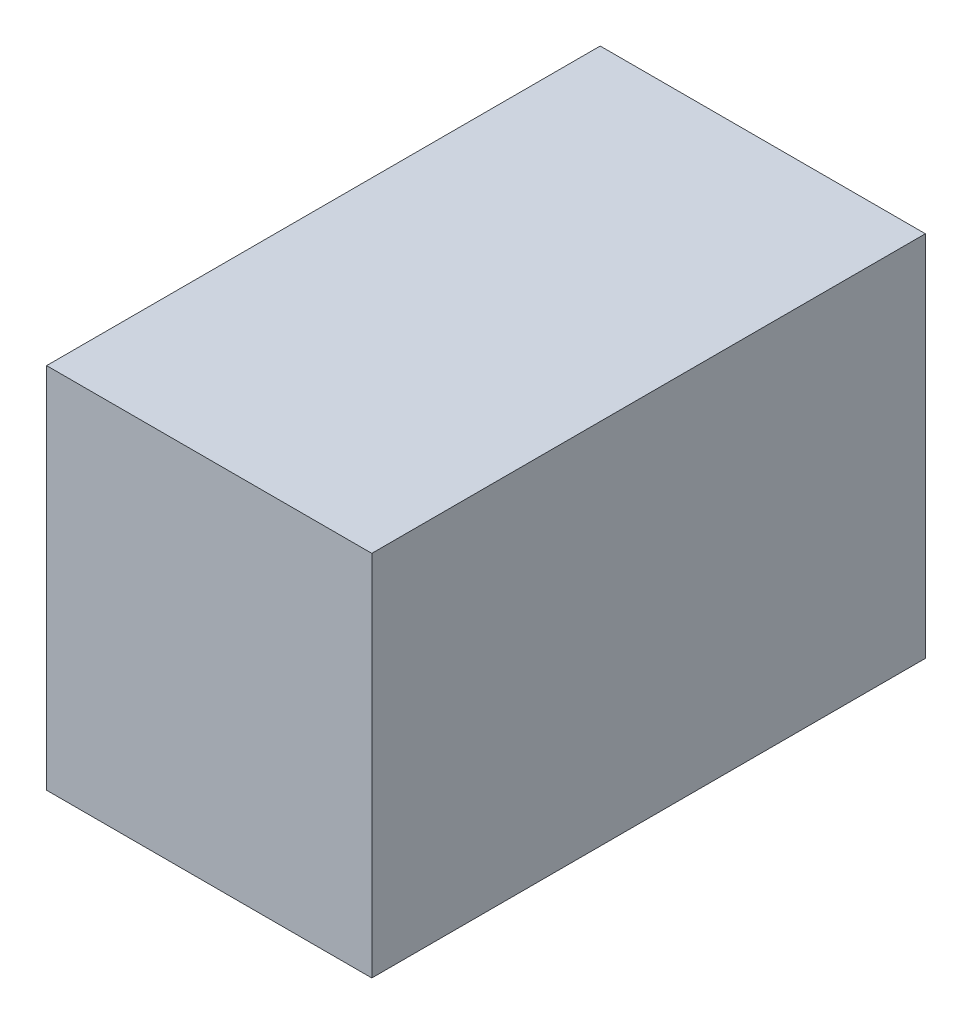
SolidWorks part; units mm, degrees
ref_plane "Front Plane" through (0, 0, 0) normal (0, 0, 1) x (1, 0, 0)
ref_plane "Top Plane" through (0, 0, 0) normal (0, 1, 0) x (1, 0, 0)
ref_plane "Right Plane" through (0, 0, 0) normal (1, 0, 0) x (0, 0, -1)
sketch "Sketch4" plane through (0, 0, 0) normal (1, 0, 0) x (0, 0, -1)
  line L1 (-15.875, 9.875) -> (15.875, 9.875)
  line L2 (-15.875, 9.875) -> (-15.875, -9.875)
  line L3 (-15.875, -9.875) -> (15.875, -9.875)
  line L4 (15.875, 9.875) -> (15.875, -9.875)
  line L5 (-15.875, 9.875) -> (15.875, -9.875) construction
  line L6 (-15.875, -9.875) -> (15.875, 9.875) construction
  point P0 (0, 0)
  dimension "D1" = 31.75
  dimension "D2" = 19.75
extrude "Boss-Extrude1" add sketch "Sketch4" along normal blind 19
shell "Shell1" thickness 2 removed face at (0, 0, 0) outward yes
sketch "Sketch5" plane through (0, 0, -17.875) normal (0, 0, -1) x (-1, 0, 0)
  line L0 (0, -11.875) -> (0, 11.875) construction
  line L1 (0, 9.875) -> (-12, 9.875)
  line L2 (-12, 9.875) -> (-12, -9.875)
  line L3 (-12, -9.875) -> (0, -9.875)
  line L4 (-21, 11.875) -> (0, 11.875) construction
  line L5 (-21, -11.875) -> (0, -11.875) construction
  line L6 (0, 9.875) -> (0, -9.875)
  dimension "D1" = 12
  dimension "D2" = 2
  dimension "D3" = 2
extrude "Cut-Extrude1" cut sketch "Sketch5" against normal up to surface (2 mm away) up to face at (9.5, 0, -15.875)
equation "\"terminalRad\"= 3mm"
equation "\"terminalLen\"= 10.5mm"
equation "\"threadlen\"=11"
